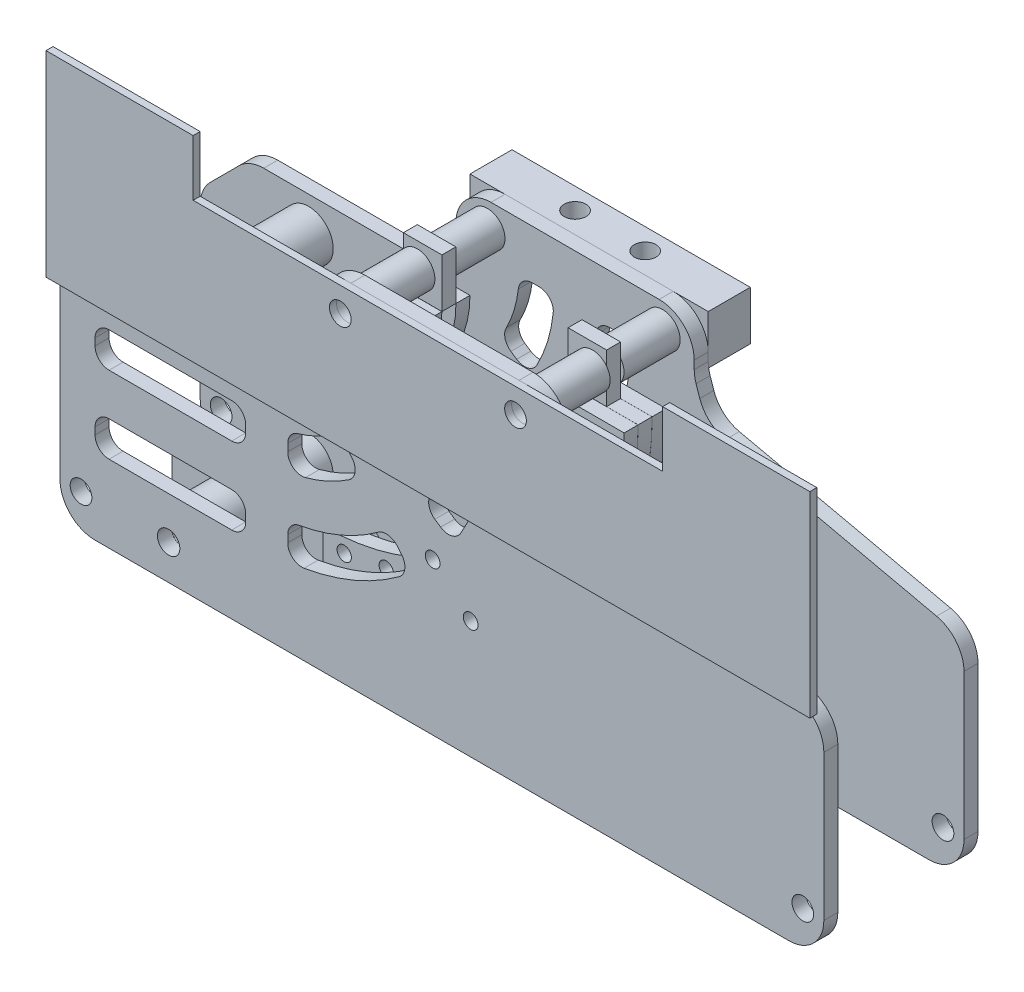
SolidWorks part; units mm, degrees
note: The reader was unsure of these and kept them because the rebuilt part matched: shared geometry of "草图19<2>", "草图25<3>", "草图35<2>".
other "标注1"
sketch "草图9" plane through (-40, -43, 13) normal (0, 0, 1) x (1, 0, 0)
material "Thornel Mat VMA"
ref_plane "前视基准面" through (0, 0, 0) normal (0, 0, 1) x (1, 0, 0)
ref_plane "上视基准面" through (0, 0, 0) normal (0, 1, 0) x (1, 0, 0)
ref_plane "右视基准面" through (0, 0, 0) normal (1, 0, 0) x (0, 0, -1)
sketch "草图1" plane through (0, 0, 0) normal (0, 0, 1) x (1, 0, 0)
  line L0 (0, 0) -> (24, 0) construction
  line L1 (0, 0) -> (0, -24) construction
  arc A1 (24, 0) -> (0, -24) centre (0, 0) cw construction
  dimension "D1" = 24
sketch "草图2" plane through (0, 0, 0) normal (0, 0, 1) x (1, 0, 0)
  line L0 (0, -24) -> (0, -15) construction
  line L1 (0, 0) -> (0, -24) construction
  line L2 (0, -24) -> (0, -33) construction
  line L3 (0, 0) -> (24, 0) construction
  line L4 (0, 0) -> (12.9505, 1.133) construction
  line L5 (0, -5) -> (0, -15)
  line L6 (15, 0) -> (5, 0)
  line L7 (33, 0) -> (43, 0)
  line L8 (0, -33) -> (0, -43)
  line L9 (0, 0) -> (42.8364, -3.7477) construction
  line L10 (0, 0) -> (14.9429, 1.3073) construction
  line L11 (0, 0) -> (34.8668, -3.0505) construction
  line L12 (0, 0) -> (33.8074, -9.0587) construction
  line L13 (0, 0) -> (12.2917, -4.2324) construction
  arc A0 (0, -15) -> (15, 0) centre (0, 0) ccw
  arc A1 (0, -33) -> (33, 0) centre (0, 0) ccw
  arc A2 (0, -5) -> (5, 0) centre (0, 0) ccw
  arc A3 (0, -43) -> (43, 0) centre (0, 0) ccw
  arc A4 (0, -13) -> (13, 0) centre (0, 0) ccw construction
  arc A5 (0, -35) -> (35, 0) centre (0, 0) ccw construction
  circle A6 centre (34.8668, -3.0505) radius 1.025
  circle A7 centre (12.9505, 1.133) radius 1.025 construction
  circle A8 centre (33.8074, -9.0587) radius 1.025
  circle A9 centre (31.7208, -14.7916) radius 1.025
  circle A10 centre (28.6703, -20.0752) radius 1.025
  circle A11 centre (24.7487, -24.7487) radius 1.025
  circle A12 centre (20.0752, -28.6703) radius 1.025
  circle A13 centre (14.7916, -31.7208) radius 1.025
  circle A14 centre (9.0587, -33.8074) radius 1.025
  circle A15 centre (3.0505, -34.8668) radius 1.025
  circle A16 centre (12.2917, -4.2324) radius 1.025
  circle A17 centre (9.5076, -8.866) radius 1.025
  circle A18 centre (5.0795, -11.9666) radius 1.025
  arc A19 (0, -8.5) -> (8.5, 0) centre (0, 0) ccw construction
  arc A20 (0, -40) -> (40, 0) centre (0, 0) ccw construction
  circle A21 centre (3.5, -7.746) radius 1.25
  circle A22 centre (7.746, -3.5) radius 1.25
  circle A23 centre (7, -39.3827) radius 1.25
  circle A24 centre (39.3827, -7) radius 1.25
  circle A25 centre (31.3827, -24.8017) radius 1.25
  dimension "D7" = 2.05
  dimension "D14" = 8.5
  dimension "D15" = 40
  dimension "D16" = 2.5
  dimension "D19" = 7
  dimension "D21" = 8
  dimension "D1" = 9
  dimension "D2" = 9
  dimension "D3" = 10
  dimension "D4" = 10
  dimension "D5" = 2
  dimension "D6" = 2
  dimension "D8" = 5
  dimension "D9" = 5
  dimension "D11" = 10
  dimension "D13" = 24
  dimension "D17" = 3.5
  dimension "D18" = 3.5
  dimension "D20" = 7
  dimension "D10" = 9
  dimension "D12" = 4
extrude "凸台-拉伸1" add sketch "草图2" along normal mid plane 6
sketch "草图5" plane through (0, 0, 0) normal (0, 0, 1) x (1, 0, 0)
  line L0 (24, 7) -> (24, -43) construction
  line L1 (-30.5, 7) -> (78.5, 7) construction
  line L2 (-30.5, 7) -> (-30.5, -5) construction
  line L3 (-30.5, -43) -> (78.5, -43) construction
  line L4 (78.5, 7) -> (78.5, -5) construction
  line L5 (43, 0) -> (33, 0) construction
  line L6 (-30.5, -24) -> (78.5, -24) construction
  line L7 (-22.5, -5) -> (0, -5)
  line L8 (-22.5, -5) -> (42.7083, -5) construction
  line L9 (-30.5, -13) -> (-30.5, -43)
  line L10 (-30.5, -43) -> (78.5, -43)
  line L11 (78.5, -13) -> (78.5, -43)
  line L12 (-30.5, -5) -> (-30.5, -24) construction
  line L13 (-30.5, -24) -> (78.5, -24) construction
  line L14 (78.5, -5) -> (42.7083, -5) construction
  line L15 (5, 0) -> (5, 7)
  line L16 (5, 7) -> (43, 7)
  line L17 (43, 7) -> (43, 0)
  line L18 (-30.5, -13) -> (-30.5, -43) construction
  line L19 (-30.5, -5) -> (-30.5, -24) construction
  line L20 (-30.5, -5) -> (-22.5, -5) construction
  line L22 (42.7083, -5) -> (78.5, -13)
  line L23 (-22.5, -5) -> (-30.5, -13)
  line L24 (-30.5, -13) -> (78.5, -13) construction
  line L25 (78.5, -5) -> (78.5, -24) construction
  line L26 (78.5, -13) -> (78.5, -43) construction
  line L27 (78.5, -5) -> (78.5, -24) construction
  line L28 (78.5, -24) -> (78.5, -13) construction
  line L29 (78.5, -24) -> (78.5, -13) construction
  line L30 (42.7083, -5) -> (78.5, -5) construction
  line L31 (-30.5, -5) -> (-22.5, -5) construction
  line L32 (-30.5, -24) -> (-30.5, -13) construction
  line L33 (-30.5, -24) -> (-30.5, -13) construction
  arc A0 (0, -43) -> (43, 0) centre (0, 0) ccw construction
  arc A1 (0, -5) -> (5, 0) centre (0, 0) ccw
  arc A2 (0, -5) -> (5, 0) centre (0, 0) ccw construction
  arc A3 (43, 0) -> (42.7083, -5) centre (0, 0) cw
  circle A4 centre (-26.5, -10) radius 1.55 construction
  circle A5 centre (-26.5, -38) radius 1.55
  circle A6 centre (74.5, -10) radius 1.55 construction
  circle A8 centre (76.5, -38) radius 1.55
  point P10 (24, -24)
  dimension "D3" = 3.1
  dimension "D6" = 30
  dimension "D8" = 2
  dimension "D1" = 7
  dimension "D2" = 109
  dimension "D4" = 4
  dimension "D5" = 28
  dimension "D7" = 8
extrude "凸台-拉伸2" add sketch "草图5" along normal blind 2 from offset 9 separate body
mirror "镜向8" about plane through (0, 0, 0) normal (0, 0, 1) of bodies 247 105
sketch "草图7" plane through (0, 0, 0) normal (0, 0, 1) x (1, 0, 0)
  line L0 (15, 0) -> (15, 7)
  line L1 (15, 7) -> (9.5, 7)
  line L2 (9.5, 7) -> (9.5, 0)
  line L3 (0, 0) -> (24, 0) construction
  line L4 (9.5, 0) -> (15, 0)
  line L5 (0, 0) -> (0, -24) construction
  line L6 (0, -15) -> (-23.5, -15)
  line L7 (0, -15) -> (0, -5)
  line L8 (0, -5) -> (-23.5, -5)
  line L9 (-30.5, -15) -> (-30.5, -5)
  line L10 (-30.5, -13) -> (-30.5, -43) construction
  line L11 (0, -43) -> (-23.5, -43)
  line L12 (0, -43) -> (0, -33)
  line L13 (0, -33) -> (-23.5, -33)
  line L14 (-30.5, -43) -> (-30.5, -33) construction
  line L15 (38.5, 0) -> (33, 0)
  line L16 (38.5, 0) -> (38.5, 7)
  line L17 (38.5, 7) -> (33, 7)
  line L18 (33, 0) -> (33, 7)
  line L19 (12.25, 7) -> (12.25, 0) construction
  line L20 (35.75, 0) -> (35.75, 7) construction
  line L21 (-23.5, -5) -> (-23.5, -15) construction
  line L22 (-23.5, -5) -> (-30.5, -5)
  line L23 (-23.5, -15) -> (-30.5, -15)
  line L24 (-23.5, -33) -> (-30.5, -33) construction
  line L25 (-23.5, -43) -> (-30.5, -43) construction
  line L26 (-23.5, -15) -> (-23.5, -33) construction
  line L27 (-23.5, -33) -> (-23.5, -43)
  arc A0 (0, -5) -> (5, 0) centre (0, 0) ccw construction
  arc A1 (0, -33) -> (33, 0) centre (0, 0) ccw construction
  arc A2 (0, -43) -> (43, 0) centre (0, 0) ccw construction
  arc A3 (0, -15) -> (15, 0) centre (0, 0) ccw construction
  dimension "D1" = 7
  dimension "D2" = 7
  dimension "D3" = 5.5
extrude "凸台-拉伸3" add sketch "草图7" along normal mid plane 2
sketch "草图8" plane through (0, 0, 0) normal (0, 0, 1) x (1, 0, 0)
  line L0 (0, 0) -> (0, -24) construction
  line L1 (0, 0) -> (24, 0) construction
  line L2 (10, 0) -> (15, 0)
  line L3 (0, -10) -> (0, -15)
  line L4 (0, -38) -> (0, -33)
  line L5 (38, 0) -> (33, 0)
  line L6 (0, -33) -> (-23.5, -33) construction
  arc A0 (15, 0) -> (0, -15) centre (0, 0) cw
  arc A1 (10, 0) -> (0, -10) centre (0, 0) cw
  arc A2 (33, 0) -> (0, -33) centre (0, 0) cw
  arc A3 (0, -33) -> (33, 0) centre (0, 0) ccw construction
  arc A4 (38, 0) -> (0, -38) centre (0, 0) cw
  dimension "D1" = 5
  dimension "D2" = 5
sketch "草图10" plane through (0, 0, 0) normal (0, 0, 1) x (1, 0, 0)
  line L0 (-19, -10) -> (0, -10) construction
  line L2 (-30.5, -38) -> (0, -38) construction
  line L4 (0, -43) -> (0, -33) construction
  line L5 (-30.5, -13) -> (-30.5, -43) construction
  circle A0 centre (-6, -10) radius 1.6 construction
  circle A1 centre (-6, -38) radius 1.6 construction
  circle A2 centre (-14, -10) radius 1.6
  circle A3 centre (-14, -38) radius 1.6
  dimension "D1" = 3.2
  dimension "D2" = 6
  dimension "D4" = 8
  dimension "D3" = 2
extrude "切除-拉伸4" cut sketch "草图10" against normal through all both and the other way through all
sketch "草图6" plane through (0, 0, 0) normal (0, 1, 0) x (1, 0, 0)
  line L1 (152.0197, -9) -> (-90.9246, -9)
  line L2 (152.0197, 9) -> (-90.2, 9)
  line L3 (152.0197, 0.99) -> (-86.3103, 0.99)
  line L4 (152.0197, 1) -> (-86.3103, 1)
  line L9 (152.0197, 0.99) -> (152.0197, 1)
  line L16 (-86.3103, 0.99) -> (-86.3103, 1)
  line L17 (152.0197, -1.01) -> (-86.3103, -1.01)
  line L18 (152.0197, -1) -> (-86.3103, -1)
  line L19 (152.0197, -1.01) -> (152.0197, -1)
  line L20 (-86.3103, -1.01) -> (-86.3103, -1)
  line L26 (152.0197, -9) -> (152.0197, -8.99)
  line L27 (152.0197, -8.99) -> (-90.9246, -8.99)
  line L28 (-90.9246, -9) -> (-90.9246, -8.99)
  line L30 (152.0197, 9) -> (152.0197, 8.99)
  line L31 (152.0197, 8.99) -> (-90.2, 8.99)
  line L32 (-90.2, 9) -> (-90.2, 8.99)
  dimension "D1" = 0.01
  dimension "D4" = 0.01
  dimension "D5" = 0.01
sketch "草图11" plane through (0, 0, 11) normal (0, 0, 1) x (1, 0, 0)
  circle A0 centre (-14, -10) radius 1.6
  circle A1 centre (-14, -10) radius 3.5
  circle A2 centre (-14, -38) radius 1.6
  circle A3 centre (-14, -38) radius 3.5
  circle A4 centre (-9, -10) radius 3.5 construction
  circle A5 centre (-9, -10) radius 1.6 construction
  circle A6 centre (-9, -38) radius 1.6 construction
  circle A7 centre (-9, -38) radius 3.5 construction
  circle A12 centre (-14, -10) radius 1.6 construction
  circle A13 centre (-14, -38) radius 1.6 construction
  dimension "D1" = 3.2
  dimension "D2" = 7
  dimension "D3" = 2
  dimension "D4" = 5
extrude "凸台-拉伸4" add sketch "草图11" against normal up to surface (22 mm away)
extrude "切除-拉伸7" cut sketch "草图6" against normal through all both and the other way through all
extrude "切除-拉伸8" cut sketch "草图8" against normal mid plane 2
sketch "草图18" plane through (0, 0, 0) normal (0, 0, 1) x (1, 0, 0)
  line L0 (12.25, 7) -> (12.25, 0) construction
  line L1 (15, 7) -> (9.5, 7) construction
  line L2 (0, 0) -> (24, 0) construction
  line L3 (35.75, 7) -> (35.75, 1.2707) construction
  line L4 (38.5, 7) -> (33, 7) construction
  line L5 (12.25, 7) -> (35.75, 7) construction
  line L6 (24, 7) -> (24, 1.2707) construction
  circle A0 centre (11.5, 3.5) radius 1.55
  circle A1 centre (36.5, 3.5) radius 1.55
  dimension "D1" = 3.1
  dimension "D2" = 3.5
  dimension "D3" = 25
extrude "切除-拉伸9" cut sketch "草图18" against normal through all both and the other way through all from offset 9
sketch "草图19" plane through (0, 0, 9) normal (0, 0, -1) x (-1, 0, 0)
  circle A0 centre (-11.5, 3.5) radius 1.55 construction
  circle A1 centre (-11.5, 3.5) radius 1.55
  circle A2 centre (-36.5, 3.5) radius 1.55 construction
  circle A3 centre (-36.5, 3.5) radius 1.55
  circle A4 centre (-11.5, 3.5) radius 2.5
  circle A5 centre (-36.5, 3.5) radius 2.5
  dimension "D1" = 5
extrude "凸台-拉伸9" add sketch "草图19" along normal up to surface (8 mm away) separate body
extrude "凸台-拉伸10" add sketch "草图19<2>" along normal up to surface (8.01 mm away) from surface at 9.99 separate body starting at face at (13.05, 3.5, -0.99)
sketch "草图19<2>" plane through (0, 0, 9) normal (0, 0, -1) x (-1, 0, 0) same geometry as "草图19"
sketch "草图20" plane through (0, 0, -11) normal (0, 0, -1) x (-1, 0, 0)
  line L1 (-5, 7) -> (-43, 7)
  line L2 (-5, 7) -> (-5, 0)
  line L3 (-5, 0) -> (-43, 0)
  line L4 (-43, 7) -> (-43, 0)
  circle A4 centre (-11.5, 3.5) radius 1.2
  circle A5 centre (-36.5, 3.5) radius 1.2
  dimension "D1" = 2.4
extrude "凸台-拉伸11" add sketch "草图20" along normal blind 6 separate body
cosmetic thread "装饰螺纹线1" parameters "D2"=3
cosmetic thread "装饰螺纹线2" parameters "D2"=3
sketch "草图21" plane through (0, 0, 0) normal (0, -1, 0) x (1, 0, 0)
  line L0 (5, -14) -> (43, -14) construction
  line L1 (5, -17) -> (5, -11) construction
  line L2 (43, -17) -> (43, -11) construction
  line L3 (24, -14) -> (24, -17) construction
  line L4 (43, -17) -> (5, -17) construction
  circle A0 centre (19, -14) radius 1.55
  circle A1 centre (29, -14) radius 1.55
  dimension "D1" = 3.1
  dimension "D2" = 10
extrude "切除-拉伸10" cut sketch "草图21" against normal through all
sketch "草图22" plane through (0, 0, 11) normal (0, 0, 1) x (1, 0, 0)
  line L0 (7, 0) -> (3.5355, -3.5355)
  line L1 (5, 7) -> (7, 7)
  line L2 (5, 7) -> (5, 0)
  line L3 (5, 0) -> (7, 0) construction
  line L4 (7, 7) -> (7, 0)
  line L5 (43, 7) -> (41, 7)
  line L6 (43, 7) -> (43, 0)
  line L7 (43, 0) -> (41, 0) construction
  line L8 (41, 7) -> (41, 0)
  line L9 (41, 0) -> (42.7083, -5)
  arc A0 (0, -5) -> (5, 0) centre (0, 0) ccw construction
  arc A1 (3.5355, -3.5355) -> (5, 0) centre (0, 0) ccw
  arc A2 (0, -5) -> (3.5355, -3.5355) centre (0, 0) ccw construction
  arc A3 (42.7083, -5) -> (43, 0) centre (0, 0) ccw construction
  arc A4 (42.7083, -5) -> (43, 0) centre (0, 0) ccw
  arc M14 (42.7083, -5) -> (43, 0) centre (0, 0) ccw
  line M15 (43, 0) -> (43, 7)
  line M16 (43, 7) -> (5, 7)
  line M17 (5, 7) -> (5, 0)
  arc M18 (5, 0) -> (0, -5) centre (0, 0) cw
  dimension "D1" = 2
extrude "切除-拉伸11" cut sketch "草图22" against normal through all both and the other way through all contours L8 L9 M14 M15 M16 | L4 L0 M16 M17 M18
sketch "草图23" plane through (0, 0, 11) normal (0, 0, 1) x (1, 0, 0)
  line L0 (23.6761, -21.3041) -> (29.1026, -26.187) construction
  line L1 (38, 0) -> (33, 0) construction
  line L2 (0, -38) -> (0, -33) construction
  line L3 (26.3894, -23.7455) -> (47.4177, -0.3759) construction
  circle A0 centre (29.1026, -26.187) radius 1.05
  circle A1 centre (23.6761, -21.3041) radius 1.05
  arc A3 (35.5, 0) -> (0, -35.5) centre (0, 0) cw construction
  point P4 (26.3894, -23.7455)
  dimension "D1" = 2.1
  dimension "D2" = 7.3
extrude "切除-拉伸12" cut sketch "草图23" against normal through all and the other way through all
sketch "草图24" plane through (0, 0, -11) normal (0, 0, -1) x (-1, 0, 0)
  line L0 (30.5, -43) -> (24.1491, -54)
  line L1 (15.4889, -59) -> (-24, -59)
  line L2 (-24, -59) -> (-24, -43) construction
  line L3 (30.5, -43) -> (-78.5, -43) construction
  line L4 (30.5, -43) -> (-24, -43)
  line L5 (15.4889, -56) -> (-21, -56)
  line L6 (-21, -56) -> (-21, -46)
  line L7 (25.3038, -46) -> (-21, -46)
  line L8 (25.3038, -46) -> (21.5511, -52.5)
  line L9 (-73.3038, -46) -> (-69.5511, -52.5)
  line L10 (-73.3038, -46) -> (-27, -46)
  line L11 (-27, -56) -> (-27, -46)
  line L12 (-63.4889, -56) -> (-27, -56)
  line L13 (-78.5, -43) -> (-24, -43)
  line L14 (-63.4889, -59) -> (-24, -59)
  line L15 (-78.5, -43) -> (-72.1491, -54)
  arc A0 (24.1491, -54) -> (15.4889, -59) centre (15.4889, -49) cw
  arc A1 (21.5511, -52.5) -> (15.4889, -56) centre (15.4889, -49) cw
  arc A2 (-69.5511, -52.5) -> (-63.4889, -56) centre (-63.4889, -49) ccw
  arc A3 (-72.1491, -54) -> (-63.4889, -59) centre (-63.4889, -49) ccw
  dimension "D1" = 10
  dimension "D2" = 16
  dimension "D4" = 60
  dimension "D3" = 3
extrude "凸台-拉伸13" [suppressed] add sketch "草图24" against normal up to surface (2 mm away)
fillet "圆角5" [suppressed] radius 2
sketch "草图25" plane through (0, 0, 11) normal (0, 0, 1) x (1, 0, 0)
  line L0 (33, 0) -> (15, 0) construction
  line L1 (0, -24) -> (-30.5, -24) construction
  line L2 (-30.5, -13) -> (-30.5, -43) construction
  line L3 (0, -27) -> (-30.5, -27)
  line L4 (0, -21) -> (-30.5, -21)
  line L5 (0, -32) -> (-30.5, -32)
  line L6 (0, -16) -> (-30.5, -16)
  line L7 (21, 0) -> (16, 0)
  line L8 (27, 0) -> (32, 0)
  line L9 (-3, -16) -> (-3, -32)
  line L10 (-30.5, -16) -> (-30.5, -21)
  line L11 (-30.5, -27) -> (-30.5, -32)
  line L12 (13.2675, -8.9428) -> (26.535, -17.8855)
  line L13 (10.2886, -12.2534) -> (20.5772, -24.5067)
  line L14 (0, 0) -> (24.531, -22.0733) construction
  line L15 (3, -15.7162) -> (3, -31.8591)
  line L16 (-24.5, -16) -> (-24.5, -32)
  arc A0 (0, -24) -> (24, 0) centre (0, 0) ccw construction
  arc A1 (0, -27) -> (27, 0) centre (0, 0) ccw
  arc A2 (0, -21) -> (21, 0) centre (0, 0) ccw
  arc A3 (0, -32) -> (32, 0) centre (0, 0) ccw
  arc A4 (0, -16) -> (16, 0) centre (0, 0) ccw
  arc A5 (0, -33) -> (33, 0) centre (0, 0) ccw construction
  circle A7 centre (23.6761, -21.3041) radius 1.05 construction
  circle A8 centre (23.6761, -21.3041) radius 1.05 construction
  dimension "D5" = 8
  dimension "D6" = 3
  dimension "D7" = 3
  dimension "D8" = 6
  dimension "D1" = 3
  dimension "D2" = 3
  dimension "D3" = 8
  dimension "D4" = 8
extrude "切除-拉伸13" cut sketch "草图25" against normal through all contours A4 L12 A2 L7 | L12 A3 L8 A1 | L15 A3 L13 A1 | A4 L15 A2 L13 | L3 L16 L5 L9 | L6 L16 L4 L9
extrude "切除-拉伸16" cut sketch "草图25<3>" against normal through all contours L6 L16 L4 L9 | L3 L16 L5 L9 | A4 L12 A2 L7 | L12 A3 L8 A1
sketch "草图25<3>" plane through (0, 0, 11) normal (0, 0, 1) x (1, 0, 0) same geometry as "草图25"
fillet "圆角6" radius 2 24 edges at (16, 0, 10) (21, 0, 10) (13.2675, -8.9428, 10) (27, 0, 10) (32, 0, 10) (26.535, -17.8855, 10) (17.362, -20.6776, 10) (20.5772, -24.5067, 10) (3, -31.8591, 10) (3, -26.8328, 10) (-3, -21, 10) (-24.5, -21, 10) (-24.5, -16, 10) (-3, -16, 10) (-3, -32, 10) (-24.5, -32, 10) (-24.5, -27, 10) (-3, -27, 10) (10.2886, -12.2534, 10) (3, -20.7846, 10) (3, -15.7162, 10) (22.3889, -15.0909, 10) (17.4136, -11.7374, 10) (13.5038, -16.0825, 10)
fillet "圆角7" radius 2 16 edges at (21, 0, -10) (17.4136, -11.7374, -10) (13.2675, -8.9428, -10) (16, 0, -10) (-3, -21, -10) (-24.5, -21, -10) (-24.5, -16, -10) (-3, -27, -10) (-3, -32, -10) (-24.5, -32, -10) (-24.5, -27, -10) (22.3889, -15.0909, -10) (27, 0, -10) (32, 0, -10) (26.535, -17.8855, -10) (-3, -16, -10)
sketch "草图27" plane through (0, 0, -11) normal (0, 0, -1) x (-1, 0, 0)
  line L0 (1.6839, -33.7195) -> (-15, -22.6901)
  line L1 (-15, -22.6901) -> (-23.2721, -35.203)
  line L2 (-23.2721, -35.203) -> (-6.5882, -46.2324)
  line L3 (-6.5882, -46.2324) -> (1.6839, -33.7195)
  line L4 (-41, 0) -> (-7, 0) construction
  line L5 (-41, 0) -> (-7, 0) construction
  line L6 (0, 0) -> (-23.2721, -35.203) construction
  arc A0 (-24, 0) -> (-1.1624, -23.9718) centre (0, 0) ccw construction
  arc A1 (-27.2, 0) -> (12.9191, -23.9361) centre (0, 0) ccw construction
  dimension "D2" = 3.2
  dimension "D1" = 15
  dimension "D3" = 20
  dimension "D4" = 9
extrude "凸台-拉伸14" add sketch "草图27" along normal blind 15 separate body
sketch "草图28" plane through (23.2721, -35.203, 0) normal (0.5515, -0.8342, 0) x (0, 0, -1)
  line L0 (22.7, -20) -> (22.7, 0) construction
  line L1 (26, -20) -> (11, -20) construction
  line L2 (26, 0) -> (11, 0) construction
  line L3 (26, 0) -> (11, 0) construction
  line L4 (11, -20) -> (11, 0) construction
  circle A0 centre (22.7, -14) radius 1.15
  circle A1 centre (22.7, -4.5) radius 1.15
  dimension "D1" = 2.3
  dimension "D2" = 2.3
  dimension "D3" = 9.5
  dimension "D4" = 4.5
  dimension "D5" = 11.7
extrude "切除-拉伸15" cut sketch "草图28" against normal blind 15
sketch "草图29" plane through (0, 0, -11) normal (0, 0, -1) x (-1, 0, 0)
  line L0 (1.6839, -33.7195) -> (-15, -22.6901) construction
  line L1 (-16.0618, -20.6695) -> (-13.7456, -17.1659)
  line L2 (-13.7456, -17.1659) -> (-7.9062, -21.0262)
  line L3 (-7.9062, -21.0262) -> (-10.2224, -24.5298)
  line L4 (-10.2224, -24.5298) -> (-16.0618, -20.6695)
  line L5 (-9.0643, -22.778) -> (-14.9037, -18.9177) construction
  line L6 (0, 0) -> (-15, -22.6901) construction
  circle A0 centre (0, 0) radius 27.2 construction
  circle A1 centre (0, 0) radius 24 construction
  dimension "D1" = 3.2
  dimension "D2" = 4.2
  dimension "D3" = 7
  dimension "D4" = 5
extrude "切除-拉伸17" cut sketch "草图29" against normal blind 2
fillet "圆角8" radius 1 4 edges at (13.7456, -17.1659, -10) (16.0618, -20.6695, -10) (7.9062, -21.0262, -10) (10.2224, -24.5298, -10)
sketch "草图30" plane through (0, 0, 11) normal (0, 0, 1) x (1, 0, 0)
  line L0 (41, 7) -> (7, 7) construction
  line L1 (-9.5, 7) -> (57.5, 7)
  line L2 (-30.5, 7) -> (-30.5, -13)
  line L3 (-30.5, -13) -> (78.5, -13)
  line L4 (78.5, 7) -> (78.5, -13)
  line L7 (78.5, -43) -> (78.5, -13) construction
  line L8 (-30.5, -5) -> (-30.5, -15) construction
  line L9 (78.5, 7) -> (78.5, 15)
  line L10 (78.5, 15) -> (57.5, 15)
  line L11 (57.5, 15) -> (57.5, 7)
  line L12 (24, 7) -> (24, 48.0876) construction
  line L13 (-9.5, 15) -> (-9.5, 7)
  line L14 (-30.5, 15) -> (-9.5, 15)
  line L15 (-30.5, 7) -> (-30.5, 15)
  line L16 (57.5, 7) -> (78.5, 7) construction
  line L17 (-30.5, 7) -> (-9.5, 7) construction
  circle A4 centre (36.5, 3.5) radius 1.55 construction
  circle A5 centre (11.5, 3.5) radius 1.55 construction
  circle A6 centre (36.5, 3.5) radius 1.55
  circle A7 centre (11.5, 3.5) radius 1.55
  dimension "D1" = 20
  dimension "D2" = 21
  dimension "D3" = 8
extrude "凸台-拉伸15" add sketch "草图30" along normal blind 1 separate body
sketch "草图31" plane through (0, 0, -26) normal (0, 0, -1) x (-1, 0, 0)
  line L0 (-21.6176, -32.7004) -> (-4.9338, -43.7298) construction
  line L1 (-15, -22.6901) -> (-23.2721, -35.203) construction
  line L2 (-6.5882, -46.2324) -> (1.6839, -33.7195) construction
  line L3 (-23.2721, -35.203) -> (-6.5882, -46.2324) construction
  line L4 (-13.2757, -38.2151) -> (-15.3511, -41.3545) construction
  circle A0 centre (-17.4467, -35.4578) radius 1.6
  circle A1 centre (-9.1047, -40.9725) radius 1.6
  dimension "D2" = 10
  dimension "D3" = 3.2
  dimension "D1" = 3
extrude "切除-拉伸18" cut sketch "草图31" against normal up to surface (17 mm away)
sketch "草图32" plane through (0, 0, 0) normal (0.8342, 0.5515, 0) x (0, 0, -1)
  line L0 (26, -33.2) -> (17, -33.2)
  line L1 (26, -27.2) -> (26, -42.2) construction
  line L2 (17, -33.2) -> (17, -42.2)
  line L3 (26, -42.2) -> (11, -42.2) construction
  line L4 (17, -42.2) -> (26, -42.2)
  line L5 (26, -42.2) -> (26, -33.2)
  line L6 (26, -27.2) -> (11, -27.2) construction
  line L7 (11, -27.2) -> (11, -42.2) construction
  dimension "D1" = 6
  dimension "D2" = 6
extrude "切除-拉伸19" cut sketch "草图32" against normal through all
sketch "草图33" plane through (0, 0, 1) normal (0, 0, 1) x (1, 0, 0)
  line L0 (-30.5, -15) -> (0, -15) construction
  line L1 (-30.5, -5) -> (-23.5, -5)
  line L2 (-30.5, -5) -> (-30.5, -15)
  line L3 (-30.5, -15) -> (-23.5, -15)
  line L4 (-23.5, -5) -> (-23.5, -15)
  line L5 (-23.5, -33) -> (-23.5, -43) construction
extrude "切除-拉伸20" cut sketch "草图33" against normal up to next (1.99 mm away)
sketch "草图34" plane through (0, 0, 0) normal (0, 0, 1) x (1, 0, 0)
  line L5 (-30.5, -43) -> (-29.5, -43)
  line L6 (-30.5, -43) -> (-30.5, -11)
  line L7 (-30.5, -11) -> (-29.5, -11)
  line L8 (-29.5, -43) -> (-29.5, -11)
  dimension "D1" = 1
  dimension "D2" = 32
extrude "切除-拉伸21" cut sketch "草图34" against normal through all both and the other way through all
sketch "草图35" plane through (0, 0, 0) normal (0, 0, 1) x (1, 0, 0)
  line L8 (78.5, -43) -> (78.5, -13)
  line L9 (78.5, -13) -> (79.5, -13.2235)
  line L10 (79.5, -13.2235) -> (79.5, -43)
  line L11 (79.5, -43) -> (78.5, -43)
  line L12 (78.5, -13) -> (42.7083, -5) construction
  dimension "D1" = 1
extrude "凸台-拉伸16" add sketch "草图35" along normal blind 2 from offset 9
extrude "凸台-拉伸17" add sketch "草图35<2>" against normal blind 2 from offset 9 offset against normal yes
sketch "草图35<2>" plane through (0, 0, 0) normal (0, 0, 1) x (1, 0, 0) same geometry as "草图35"
fillet "圆角9" radius 5 8 edges at (-29.5, -12, 10) (-22.5, -5, 10) (7, 7, 10) (41, 7, 10) (42.7083, -5, 10) (79.5, -13.2235, 10) (-29.5, -43, 10) (79.5, -43, 10)
fillet "圆角10" radius 5 9 edges at (-29.5, -43, -10) (79.5, -43, -10) (79.5, -13.2235, -10) (42.7083, -5, -10) (41, 7, -10) (7, 7, -10) (-29.5, -12, -10) (-22.5, -5, -10)
